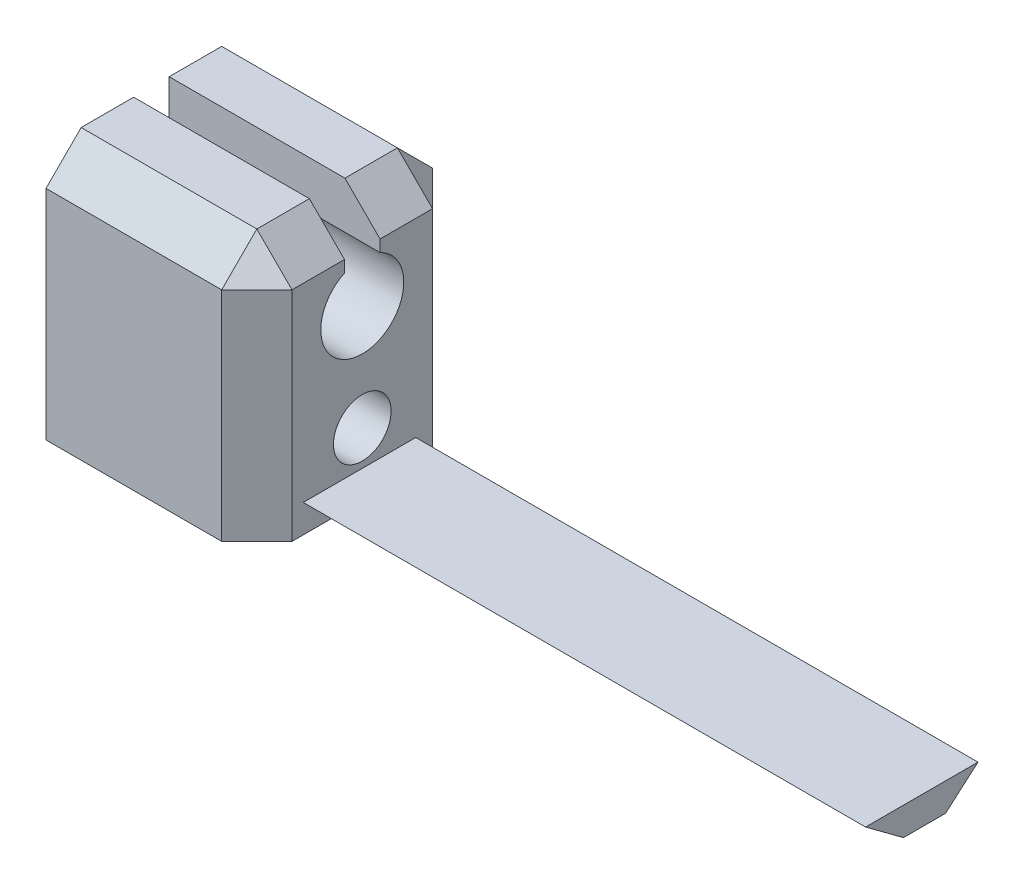
SolidWorks part; units mm, degrees
ref_plane "Front Plane" through (0, 0, 0) normal (0, 0, 1) x (1, 0, 0)
ref_plane "Top Plane" through (0, 0, 0) normal (0, 1, 0) x (1, 0, 0)
ref_plane "Right Plane" through (0, 0, 0) normal (1, 0, 0) x (0, 0, -1)
sketch "Sketch2" plane through (0, 0, 0) normal (0, 1, 0) x (1, 0, 0)
  line L1 (-15, -15) -> (15, -15)
  line L2 (-15, -15) -> (-15, 15)
  line L3 (-15, 15) -> (15, 15)
  line L4 (15, -15) -> (15, 15)
  line L5 (-15, -15) -> (15, 15) construction
  line L6 (-15, 15) -> (15, -15) construction
  point P0 (0, 0)
  dimension "D1" = 30
  dimension "D2" = 30
extrude "Boss-Extrude1" add sketch "Sketch2" along normal blind 36
sketch "Sketch4" plane through (15, 0, 0) normal (1, 0, 0) x (0, 0, -1)
  line L0 (55, 0) -> (-55, 0) construction
  line L1 (-8.3924, 0) -> (7.6076, 0)
  line L2 (-8.3924, 0) -> (-8.3924, 4)
  line L3 (-8.3924, 4) -> (7.6076, 4)
  line L4 (7.6076, 0) -> (7.6076, 4)
  line L5 (0, 0) -> (-3, 0)
  line L6 (-3, 0) -> (-8.3924, 4)
  line L7 (0, 0) -> (3, 0)
  line L8 (3, 0) -> (7.6076, 4)
  line M5 (-15, 0) -> (15, 0)
  dimension "D1" = 16
  dimension "D2" = 4
  dimension "D3" = 3
extrude "Boss-Extrude2" add sketch "Sketch4" along normal blind 80 contours L8 L3 L6 L1 M5 region at (15, 2.303, 0.2259)
sketch "Sketch5" plane through (15, 0, 0) normal (1, 0, 0) x (0, 0, -1)
  line L0 (0, 19.8) -> (0, -19.8) construction
  line L1 (16.5, 0) -> (-16.5, 0) construction
  circle A0 centre (0, 9) radius 4.1
  dimension "D2" = 8.2
  dimension "D1" = 9
extrude "Cut-Extrude1" cut sketch "Sketch5" against normal blind 80
sketch "Sketch6" plane through (15, 0, 0) normal (1, 0, 0) x (0, 0, -1)
  line L0 (0, 0) -> (0, 24)
  line L1 (0, 19.8) -> (0, -19.8) construction
  line L2 (-2.5286, 36.3305) -> (3.5722, 36.3305)
  line L3 (-15, 36) -> (15, 36) construction
  line L4 (-2.5286, 36) -> (-2.5286, 29.3307)
  line L6 (2.5286, 36) -> (2.5286, 29.3307)
  line L7 (-2.5286, 36) -> (-2.5286, 36.3305)
  line L9 (2.5286, 36.3305) -> (2.5286, 36)
  circle A0 centre (0, 24) radius 5.9
  line M11 (15, 36) -> (-15, 36)
  dimension "D1" = 11.8
extrude "Cut-Extrude2" cut sketch "Sketch6" against normal blind 80 and the other way blind 80 contours A0 | A0 L6 L4 M11 | L9 L2 L7 M11 | A0 region at (15, 36.1653, 0) region at (15, 32.8548, 0) region at (15, 29.7331, 0)
chamfer "Chamfer1" distance 5 angle 45 6 edges at (15, 36, -8.7643) (0, 36, -15) (15, 36, 8.7643) (0, 36, 15) (15, 18, -15) (15, 18, 15)
